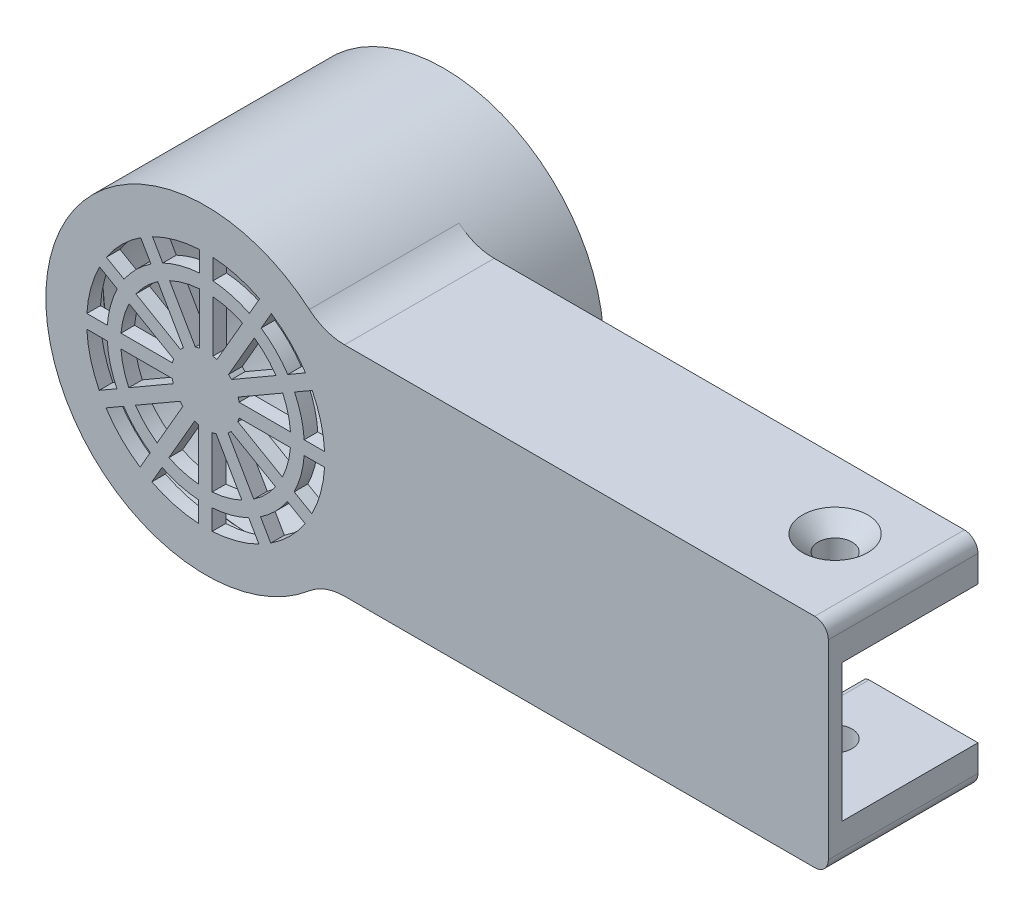
SolidWorks part; units mm, degrees
ref_plane "前视基准面" through (0, 0, 0) normal (0, 0, 1) x (1, 0, 0)
ref_plane "上视基准面" through (0, 0, 0) normal (0, 1, 0) x (1, 0, 0)
ref_plane "右视基准面" through (0, 0, 0) normal (1, 0, 0) x (0, 0, -1)
sketch "草图1" plane through (0, 0, 0) normal (0, 0, 1) x (1, 0, 0)
  circle A2 centre (0, 0) radius 21.5
  circle A3 centre (0, 0) radius 23.5
  dimension "D1" = 43
  dimension "D2" = 2
extrude "凸台-拉伸1" add sketch "草图1" against normal blind 33
sketch "草图2" plane through (0, 0, 0) normal (0, 0, -1) x (-1, 0, 0)
  line L17 (-23.5, 0) -> (-23.5, -21.8678) construction
  line L18 (-86.5, 16) -> (-17.2119, 16)
  line L19 (-86.5, 16) -> (-86.5, -16)
  line L20 (-86.5, -16) -> (-17.2119, -16)
  line L22 (-86.5, 16) -> (0, 0) construction
  line L23 (-86.5, -16) -> (0, 0) construction
  circle A0 centre (0, 0) radius 23.5 construction
  arc A1 (-17.2119, 16) -> (-17.2119, -16) centre (0, 0) ccw
  point P0 (0, 0)
  point P1 (0, 0)
  point P3 (0, 0)
  dimension "D1" = 32
  dimension "D2" = 63
extrude "凸台-拉伸2" add sketch "草图2" along normal blind 20
sketch "草图3" plane through (0, 0, 0) normal (0, 0, 1) x (1, 0, 0)
  line L7 (17.2119, -16) -> (86.5, -16)
  line L8 (17.2119, -16) -> (86.5, -16)
  line L9 (86.5, -16) -> (86.5, 16)
  line L10 (86.5, -16) -> (86.5, 16)
  line L11 (86.5, 16) -> (17.2119, 16)
  line L12 (86.5, 16) -> (17.2119, 16)
  circle A2 centre (0, 0) radius 20.75
  arc A4 (17.2119, 16) -> (17.2119, -16) centre (0, 0) ccw
  arc A8 (17.2119, 16) -> (17.2119, -16) centre (0, 0) ccw
  dimension "D1" = 0
extrude "凸台-拉伸4" add sketch "草图3" along normal blind 2
sketch "草图4" plane through (0, 0, 2) normal (0, 0, 1) x (1, 0, 0)
  line L4 (17.2119, -16) -> (86.5, -16)
  line L5 (17.2119, -16) -> (86.5, -16)
  line L6 (86.5, -16) -> (86.5, 16)
  line L7 (86.5, -16) -> (86.5, 16)
  line L8 (86.5, 16) -> (17.2119, 16)
  line L9 (86.5, 16) -> (17.2119, 16)
  arc A2 (17.2119, 16) -> (17.2119, -16) centre (0, 0) ccw
  arc A4 (17.2119, 16) -> (17.2119, -16) centre (0, 0) ccw
  dimension "D1" = 0
extrude "凸台-拉伸5" add sketch "草图4" against normal blind 1
sketch "草图6" plane through (0, 0, 2) normal (0, 0, 1) x (1, 0, 0)
  circle A0 centre (0, 0) radius 17.5
  arc A1 (17.2119, 16) -> (17.2119, -16) centre (0, 0) ccw construction
  dimension "D1" = 6
extrude "切除-拉伸2" cut sketch "草图6" against normal blind 1
sketch "草图7" plane through (86.5, 0, 0) normal (1, 0, 0) x (0, 0, -1)
  line L6 (11, 16) -> (9, -16) construction
  line L7 (20, 16) -> (-2, 16) construction
  line L8 (20, -16) -> (-2, -16) construction
  line L10 (-2, -16) -> (-2, 16) construction
  line L11 (-2, 0) -> (20, 0) construction
  line L12 (20, 16) -> (20, -16) construction
  line L13 (0, 10.1) -> (20, 10.1)
  line L14 (0, 10.1) -> (0, -10.1)
  line L15 (0, -10.1) -> (20, -10.1)
  line L16 (20, 10.1) -> (20, -10.1)
  line L17 (0, 10.1) -> (20, -10.1) construction
  line L18 (0, -10.1) -> (20, 10.1) construction
  point P7 (10, 0)
  dimension "D1" = 2
  dimension "D2" = 20.2
  dimension "D3" = 0
extrude "切除-拉伸3" cut sketch "草图7" against normal blind 49
sketch "草图9" plane through (0, 0, 1) normal (0, 0, -1) x (-1, 0, 0)
  circle A1 centre (0, 0) radius 20.75
  circle A5 centre (0, 0) radius 20.75
  dimension "D1" = 0
extrude "凸台-拉伸8" add sketch "草图9" along normal blind 1
sketch "草图10" plane through (0, 0, 1) normal (0, 0, 1) x (1, 0, 0)
  circle A1 centre (0, 0) radius 17.5
  circle A4 centre (0, 0) radius 17.5
  dimension "D1" = 0
extrude "切除-拉伸4" cut sketch "草图10" against normal blind 10
sketch "草图11" plane through (0, 0, 2) normal (0, 0, 1) x (1, 0, 0)
  line L0 (-16.6431, 10.8266) -> (-11.9968, 8.1441)
  line L1 (-19.8266, 1.0545) -> (-14.4616, 1.0545)
  line L2 (-19.8266, 1.0545) -> (-19.8266, -0.9455)
  line L3 (-19.8266, -0.9455) -> (-14.4691, -0.9455)
  line L5 (-16.6431, 10.8266) -> (-17.6431, 9.0945)
  line L6 (-17.6431, 9.0945) -> (-13.0034, 6.4158)
  line L7 (-9.0001, 17.6976) -> (-6.3175, 13.0514)
  line L8 (-9.0001, 17.6976) -> (-10.7321, 16.6976)
  line L9 (-10.7321, 16.6976) -> (-8.0534, 12.0579)
  line L10 (1.0545, 19.8266) -> (1.0545, 14.4616)
  line L11 (1.0545, 19.8266) -> (-0.9455, 19.8266)
  line L12 (-0.9455, 19.8266) -> (-0.9455, 14.4691)
  line L13 (10.8266, 16.6431) -> (8.1441, 11.9968)
  line L14 (10.8266, 16.6431) -> (9.0945, 17.6431)
  line L15 (9.0945, 17.6431) -> (6.4158, 13.0034)
  line L16 (17.6976, 9.0001) -> (13.0514, 6.3175)
  line L17 (17.6976, 9.0001) -> (16.6976, 10.7321)
  line L18 (16.6976, 10.7321) -> (12.0579, 8.0534)
  line L19 (19.8266, -1.0545) -> (14.4616, -1.0545)
  line L20 (19.8266, -1.0545) -> (19.8266, 0.9455)
  line L21 (19.8266, 0.9455) -> (14.4691, 0.9455)
  line L22 (16.6431, -10.8266) -> (11.9968, -8.1441)
  line L23 (16.6431, -10.8266) -> (17.6431, -9.0945)
  line L24 (17.6431, -9.0945) -> (13.0034, -6.4158)
  line L25 (9.0001, -17.6976) -> (6.3175, -13.0514)
  line L26 (9.0001, -17.6976) -> (10.7321, -16.6976)
  line L27 (10.7321, -16.6976) -> (8.0534, -12.0579)
  line L28 (-1.0545, -19.8266) -> (-1.0545, -14.4616)
  line L29 (-1.0545, -19.8266) -> (0.9455, -19.8266)
  line L30 (0.9455, -19.8266) -> (0.9455, -14.4691)
  line L31 (-10.8266, -16.6431) -> (-8.1441, -11.9968)
  line L32 (-10.8266, -16.6431) -> (-9.0945, -17.6431)
  line L33 (-9.0945, -17.6431) -> (-6.4158, -13.0034)
  line L34 (-17.6976, -9.0001) -> (-13.0514, -6.3175)
  line L35 (-17.6976, -9.0001) -> (-16.6976, -10.7321)
  line L36 (-16.6976, -10.7321) -> (-12.0579, -8.0534)
  line L37 (-11.267, 5.4133) -> (-4.7247, 1.6361)
  line L38 (-10.2595, 7.141) -> (-3.7055, 3.357)
  line L39 (-7.0509, 10.3216) -> (-3.2737, 3.7793)
  line L40 (-5.3145, 11.314) -> (-1.5305, 4.76)
  line L41 (-0.9455, 12.4642) -> (-0.9455, 4.9098)
  line L42 (1.0545, 12.4554) -> (1.0545, 4.8875)
  line L43 (5.4133, 11.267) -> (1.6361, 4.7247)
  line L44 (7.141, 10.2595) -> (3.357, 3.7055)
  line L45 (10.3216, 7.0509) -> (3.7793, 3.2737)
  line L46 (11.314, 5.3145) -> (4.76, 1.5305)
  line L47 (-11.314, -5.3145) -> (-4.76, -1.5305)
  line L48 (-10.3216, -7.0509) -> (-3.7793, -3.2737)
  line L49 (-7.141, -10.2595) -> (-3.357, -3.7055)
  line L50 (-5.4133, -11.267) -> (-1.6361, -4.7247)
  line L51 (-1.0545, -12.4554) -> (-1.0545, -4.8875)
  line L52 (0.9455, -12.4642) -> (0.9455, -4.9098)
  line L53 (5.3145, -11.314) -> (1.5305, -4.76)
  line L54 (7.0509, -10.3216) -> (3.2737, -3.7793)
  line L55 (10.2595, -7.141) -> (3.7055, -3.357)
  line L56 (11.267, -5.4133) -> (4.7247, -1.6361)
  line L57 (12.4554, -1.0545) -> (4.8875, -1.0545)
  line L58 (12.4642, 0.9455) -> (4.9098, 0.9455)
  line L59 (-12.4554, 1.0545) -> (-4.8875, 1.0545)
  line L60 (-12.4642, -0.9455) -> (-4.9098, -0.9455)
  arc A0 (-4.9098, -0.9455) -> (-4.76, -1.5305) centre (0, 0) ccw
  arc A1 (-12.4642, -0.9455) -> (-11.314, -5.3145) centre (0, 0) ccw
  arc A2 (-14.4691, -0.9455) -> (-13.0514, -6.3175) centre (0, 0) ccw
  circle A3 centre (0, 0) radius 17.5 construction
  arc A4 (-13.0034, 6.4158) -> (-14.4616, 1.0545) centre (0, 0) ccw
  arc A5 (-11.267, 5.4133) -> (-12.4554, 1.0545) centre (0, 0) ccw
  arc A6 (12.0579, 8.0534) -> (8.1441, 11.9968) centre (0, 0) ccw
  arc A7 (10.3216, 7.0509) -> (7.141, 10.2595) centre (0, 0) ccw
  arc A8 (3.7793, 3.2737) -> (3.357, 3.7055) centre (0, 0) ccw
  arc A9 (1.6361, 4.7247) -> (1.0545, 4.8875) centre (0, 0) ccw
  arc A10 (-0.9455, 4.9098) -> (-1.5305, 4.76) centre (0, 0) ccw
  arc A11 (-3.2737, 3.7793) -> (-3.7055, 3.357) centre (0, 0) ccw
  arc A12 (-4.7247, 1.6361) -> (-4.8875, 1.0545) centre (0, 0) ccw
  arc A13 (-8.0534, 12.0579) -> (-11.9968, 8.1441) centre (0, 0) ccw
  arc A14 (-7.0509, 10.3216) -> (-10.2595, 7.141) centre (0, 0) ccw
  arc A15 (-0.9455, 14.4691) -> (-6.3175, 13.0514) centre (0, 0) ccw
  arc A16 (-0.9455, 12.4642) -> (-5.3145, 11.314) centre (0, 0) ccw
  arc A17 (6.4158, 13.0034) -> (1.0545, 14.4616) centre (0, 0) ccw
  arc A18 (5.4133, 11.267) -> (1.0545, 12.4554) centre (0, 0) ccw
  arc A19 (12.4642, 0.9455) -> (11.314, 5.3145) centre (0, 0) ccw
  arc A20 (14.4691, 0.9455) -> (13.0514, 6.3175) centre (0, 0) ccw
  arc A21 (11.267, -5.4133) -> (12.4554, -1.0545) centre (0, 0) ccw
  arc A22 (13.0034, -6.4158) -> (14.4616, -1.0545) centre (0, 0) ccw
  arc A23 (4.9098, 0.9455) -> (4.76, 1.5305) centre (0, 0) ccw
  arc A24 (4.7247, -1.6361) -> (4.8875, -1.0545) centre (0, 0) ccw
  arc A25 (3.2737, -3.7793) -> (3.7055, -3.357) centre (0, 0) ccw
  arc A26 (0.9455, -4.9098) -> (1.5305, -4.76) centre (0, 0) ccw
  arc A27 (-1.6361, -4.7247) -> (-1.0545, -4.8875) centre (0, 0) ccw
  arc A28 (-3.7793, -3.2737) -> (-3.357, -3.7055) centre (0, 0) ccw
  arc A29 (-10.3216, -7.0509) -> (-7.141, -10.2595) centre (0, 0) ccw
  arc A30 (-12.0579, -8.0534) -> (-8.1441, -11.9968) centre (0, 0) ccw
  arc A31 (-5.4133, -11.267) -> (-1.0545, -12.4554) centre (0, 0) ccw
  arc A32 (-6.4158, -13.0034) -> (-1.0545, -14.4616) centre (0, 0) ccw
  arc A33 (0.9455, -12.4642) -> (5.3145, -11.314) centre (0, 0) ccw
  arc A34 (0.9455, -14.4691) -> (6.3175, -13.0514) centre (0, 0) ccw
  arc A35 (7.0509, -10.3216) -> (10.2595, -7.141) centre (0, 0) ccw
  arc A36 (8.0534, -12.0579) -> (11.9968, -8.1441) centre (0, 0) ccw
  point P59 (0, 0)
  dimension "D1" = 10
  dimension "D2" = 2
  dimension "D3" = 3
  dimension "D4" = 2
  dimension "D5" = 12
extrude "凸台-拉伸9" add sketch "草图11" against normal blind 2
sketch "草图15" plane through (0, 0, -33) normal (0, 0, -1) x (-1, 0, 0)
  circle A0 centre (0, 0) radius 22.5
  circle A1 centre (0, 0) radius 23.5 construction
  dimension "D1" = 1
extrude "切除-拉伸6" cut sketch "草图15" against normal blind 1
sketch "草图16" plane through (0, 0, -20) normal (0, 0, -1) x (-1, 0, 0)
  line L2 (-86.5, -16) -> (-17.2119, -16) construction
  line L3 (-23.5, 16) -> (-23.5, -16) construction
  line L4 (-86.5, 10.1) -> (-86.5, -10.1) construction
  line L5 (-86.5, 0) -> (0, 0) construction
  line L6 (-74.5, 14.1) -> (-23.5, 14.1)
  line L7 (-74.5, 14.1) -> (-74.5, -14.1)
  line L8 (-74.5, -14.1) -> (-23.5, -14.1)
  line L9 (-23.5, 14.1) -> (-23.5, -14.1)
  line L10 (-74.5, 14.1) -> (-23.5, -14.1) construction
  line L11 (-74.5, -14.1) -> (-23.5, 14.1) construction
  point P11 (-49, 0)
  point P19 (-23.5, 0)
  dimension "D1" = 51
  dimension "D2" = 28.2
  dimension "D3" = 0
extrude "切除-拉伸7" cut sketch "草图16" against normal up to surface (20 mm away) up to face at (62, 0, 0)
sketch "草图17" plane through (0, 10.1, 0) normal (0, -1, 0) x (1, 0, 0)
  line L0 (74.5, -10) -> (86.5, -10) construction
  line L1 (74.5, 0) -> (74.5, -20) construction
  line L2 (86.5, -20) -> (86.5, 0) construction
  line L4 (74.5, 0) -> (86.5, 0) construction
  line L5 (80.5, 0) -> (80.5, -20) construction
  line L6 (74.5, -20) -> (86.5, -20) construction
  circle A0 centre (80.5, -10) radius 2.5
  dimension "D1" = 5
extrude "切除-拉伸8" cut sketch "草图17" against normal blind 21 and the other way blind 48
chamfer "倒角1" distance 2.3 angle 45 2 edges at (80.5, 16, -12.5) (80.5, -16, -7.5)
sketch "草图18" plane through (0, 0, 0) normal (0, 0, -1) x (-1, 0, 0)
  circle A0 centre (0, 0) radius 21.5
  circle A1 centre (0, 0) radius 21.1
  dimension "D1" = 42.2
extrude "凸台-拉伸10" add sketch "草图18" along normal blind 5
sketch "草图19" plane through (23.5, 0, 0) normal (1, 0, 0) x (0, 0, -1)
  line L6 (0, -10.1) -> (20, -10.1) construction
  line L7 (0, 10.1) -> (18, 10.1)
  line L8 (0, 10.1) -> (0, -10.1)
  line L9 (0, -10.1) -> (18, -10.1)
  line L10 (18, 10.1) -> (18, -10.1)
  dimension "D1" = 18
extrude "切除-拉伸9" cut sketch "草图19" against normal blind 16
sketch "草图21" plane through (0, 0, -20) normal (0, 0, -1) x (-1, 0, 0)
  line L0 (-51.856, 16) -> (-51.856, -16) construction
  line L1 (-17.2119, 16) -> (-86.5, 16) construction
  line L2 (-86.5, -16) -> (-17.2119, -16) construction
  line L4 (-86.5, 10.1) -> (-86.5, -10.1) construction
  line L5 (-86.5, 0) -> (-23.5, 0) construction
  circle A0 centre (0, 0) radius 23.5 construction
  circle A1 centre (-81.856, 13) radius 0.95
  circle A4 centre (-81.856, -13) radius 0.95
  circle A5 centre (-22.356, 14) radius 0.95
  circle A6 centre (-22.356, -14) radius 0.95
  dimension "D1" = 1.9
  dimension "D4" = 1.9
  dimension "D2" = 30
  dimension "D3" = 13
  dimension "D5" = 29.5
  dimension "D6" = 14
extrude "切除-拉伸11" cut sketch "草图21" against normal blind 6
fillet "圆角7" radius 1 2 edges at (74.5, 10.1, -10) (74.5, -10.1, -10)
sketch "草图23" plane through (0, 0, 2) normal (0, 0, 1) x (1, 0, 0)
  line L0 (51.856, 16) -> (51.856, -16) construction
  line L1 (86.5, 16) -> (17.2119, 16) construction
  line L2 (17.2119, -16) -> (86.5, -16) construction
  line L4 (-30.9151, 0) -> (86.5, 0) construction
  line L5 (86.5, -16) -> (86.5, 16) construction
  line L6 (29.856, 11) -> (73.856, 11)
  line L7 (26.856, 8) -> (26.856, -8)
  line L8 (29.856, -11) -> (73.856, -11)
  line L9 (76.856, 8) -> (76.856, -8)
  line L10 (26.856, 11) -> (76.856, -11) construction
  line L11 (26.856, -11) -> (76.856, 11) construction
  arc A0 (73.856, 11) -> (76.856, 8) centre (73.856, 8) cw
  arc A1 (73.856, -11) -> (76.856, -8) centre (73.856, -8) ccw
  arc A2 (26.856, -8) -> (29.856, -11) centre (29.856, -8) ccw
  arc A3 (29.856, 11) -> (26.856, 8) centre (29.856, 8) ccw
  point P10 (51.856, 0)
  dimension "D3" = 3
  dimension "D1" = 22
  dimension "D2" = 50
fillet "圆角13" radius 8 2 edges at (17.2119, 16, -9) (17.2119, -16, -9)
sketch "草图24" plane through (86.5, 0, 0) normal (1, 0, 0) x (0, 0, -1)
  line L8 (20, -16) -> (20, -10.1)
  line L9 (20, -10.1) -> (0, -10.1)
  line L10 (0, -10.1) -> (0, 10.1)
  line L11 (0, 10.1) -> (20, 10.1)
  line L12 (20, 10.1) -> (20, 16)
  line L13 (20, 16) -> (-2, 16)
  line L14 (-2, 16) -> (-2, -16)
  line L15 (-2, -16) -> (20, -16)
  line L16 (20, -16) -> (20, -10.1)
  line L17 (20, -10.1) -> (0, -10.1)
  line L18 (0, -10.1) -> (0, 10.1)
  line L19 (0, 10.1) -> (20, 10.1)
  line L20 (20, 10.1) -> (20, 16)
  line L21 (20, 16) -> (-2, 16)
  line L22 (-2, 16) -> (-2, -16)
  line L23 (-2, -16) -> (20, -16)
  dimension "D1" = 0
extrude "凸台-拉伸11" add sketch "草图24" along normal blind 5
chamfer "倒角2" distance 1 angle 45 4 edges at (21.0128, -10.1, 0) (21.0128, 10.1, 0) (21.24, -10.1, -18) (21.24, 10.1, -18)
fillet "圆角16" radius 2 2 edges at (91.5, 16, -9) (91.5, -16, -9)
chamfer "倒角3" distance 1 angle 45 1 edges at (-21.1, 0, -5)
